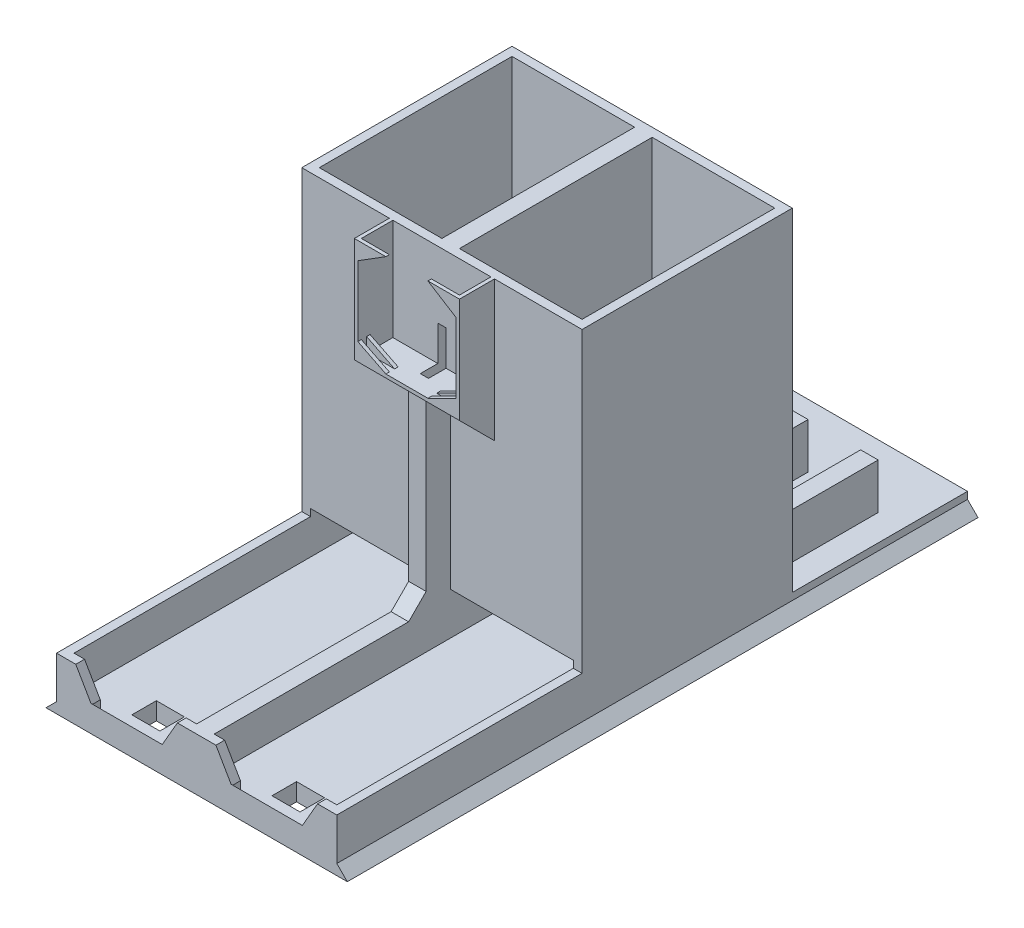
SolidWorks part; units mm, degrees
ref_plane "Front Plane" through (0, 0, 0) normal (0, 0, 1) x (1, 0, 0)
ref_plane "Top Plane" through (0, 0, 0) normal (0, 1, 0) x (1, 0, 0)
ref_plane "Right Plane" through (0, 0, 0) normal (1, 0, 0) x (0, 0, -1)
sketch "Sketch1" plane through (0, 0, 0) normal (0, 1, 0) x (1, 0, 0)
  line L1 (0, 0) -> (80, 0)
  line L2 (0, 0) -> (0, 60)
  line L3 (0, 60) -> (80, 60)
  line L4 (80, 0) -> (80, 60)
sketch "Sketch2" plane through (0, 0, 0) normal (0, 1, 0) x (1, 0, 0)
  line L1 (2.5, 57.5) -> (37.5, 57.5)
  line L2 (2.5, 57.5) -> (2.5, 2.5)
  line L3 (2.5, 2.5) -> (37.5, 2.5)
  line L4 (37.5, 57.5) -> (37.5, 2.5)
  line L5 (42.5, 57.5) -> (77.5, 57.5)
  line L6 (42.5, 57.5) -> (42.5, 2.5)
  line L7 (42.5, 2.5) -> (77.5, 2.5)
  line L8 (77.5, 57.5) -> (77.5, 2.5)
  dimension "D1" = 35
extrude "Boss-Extrude1" add sketch "Sketch1" along normal blind 100
extrude "Cut-Extrude1" cut sketch "Sketch2" along normal blind 95 from offset 5
sketch "Sketch3" plane through (0, 0, 0) normal (0, 0, 1) x (1, 0, 0)
  line L0 (80, 100) -> (80, 0) construction
  line L1 (0, 0) -> (80, 0)
  line L2 (0, 0) -> (0, 5)
  line L3 (0, 5) -> (80, 5)
  line L4 (80, 0) -> (80, 5)
extrude "Boss-Extrude2" add sketch "Sketch3" along normal blind 70
sketch "Sketch4" plane through (0, 5, 0) normal (0, 1, 0) x (1, 0, 0)
  line L0 (80, 0) -> (77.5, 0)
  line L5 (0, 0) -> (0, -70)
  line L18 (0, -70) -> (80, -70)
  line L19 (80, -70) -> (80, 0)
  line L20 (80, 0) -> (0, 0) construction
  line L21 (77.5, 0) -> (77.5, -67.5)
  line L22 (77.5, -67.5) -> (42.5, -67.5)
  line L23 (42.5, -67.5) -> (42.5, 0)
  line L24 (0, 0) -> (80, 0) construction
  line L25 (42.5, 0) -> (37.5, 0)
  line L26 (37.5, 0) -> (37.5, -67.5)
  line L27 (37.5, -67.5) -> (2.5, -67.5)
  line L28 (2.5, -67.5) -> (2.5, 0)
  line L29 (2.5, 0) -> (0, 0)
extrude "Boss-Extrude3" add sketch "Sketch4" along normal blind 10
sketch "Sketch5" plane through (0, 15, 0) normal (0, 1, 0) x (1, 0, 0)
  line L0 (37.5, -67.5) -> (2.5, -67.5) construction
  line L1 (10, -67.5) -> (30, -67.5)
  line L2 (10, -67.5) -> (10, -70)
  line L3 (10, -70) -> (30, -70)
  line L4 (30, -67.5) -> (30, -70)
  line L5 (0, -70) -> (80, -70) construction
  line L6 (77.5, -67.5) -> (42.5, -67.5) construction
  line L7 (70, -67.5) -> (50, -67.5)
  line L8 (70, -67.5) -> (70, -70)
  line L9 (70, -70) -> (50, -70)
  line L10 (50, -67.5) -> (50, -70)
  line L12 (37.5, 0) -> (37.5, -67.5) construction
  line L13 (42.5, -67.5) -> (42.5, 0) construction
  line L14 (77.5, 0) -> (77.5, -67.5) construction
  line L15 (2.5, -67.5) -> (2.5, 0) construction
  dimension "D1" = 7.5
  dimension "D2" = 7.5
  dimension "D3" = 7.5
  dimension "D4" = 7.5
extrude "Cut-Extrude2" cut sketch "Sketch5" against normal blind 7.5
sketch "Sketch6" plane through (0, 0, 0) normal (0, 0, 1) x (1, 0, 0)
  line L1 (2.5, 17) -> (37.5, 17)
  line L2 (2.5, 17) -> (2.5, 5)
  line L3 (2.5, 5) -> (37.5, 5)
  line L4 (37.5, 17) -> (37.5, 5)
  line L5 (42.5, 5) -> (77.5, 5)
  line L6 (42.5, 5) -> (42.5, 17)
  line L7 (42.5, 17) -> (77.5, 17)
  line L8 (77.5, 5) -> (77.5, 17)
extrude "Cut-Extrude4" cut sketch "Sketch6" against normal blind 57.5
sketch "Sketch7" plane through (0, 0, -60) normal (0, 0, -1) x (-1, 0, 0)
  circle A0 centre (-20, 11.5) radius 4
  circle A1 centre (-60, 11.5) radius 4
extrude "Cut-Extrude6" cut sketch "Sketch7" against normal up to next
sketch "Sketch9" plane through (0, 0, 0) normal (0, 1, 0) x (1, 0, 0)
  line L1 (0, 60) -> (80, 60)
  line L2 (0, 60) -> (0, 110)
  line L3 (0, 110) -> (80, 110)
  line L4 (80, 60) -> (80, 110)
extrude "Boss-Extrude4" add sketch "Sketch9" along normal blind 5
sketch "Sketch13" plane through (0, 5, 0) normal (0, 1, 0) x (1, 0, 0)
  line L1 (16, -64.5) -> (24, -64.5)
  line L2 (16, -64.5) -> (16, -57.5)
  line L3 (16, -57.5) -> (24, -57.5)
  line L4 (24, -64.5) -> (24, -57.5)
  line L5 (30, -67.5) -> (10, -67.5) construction
  line L10 (2.5, 57.5) -> (2.5, -67.5) construction
  line L11 (37.5, -67.5) -> (37.5, 57.5) construction
  line L12 (40, -70) -> (40, -52.9537) construction
  line L13 (30, -70) -> (50, -70) construction
  line L15 (56, -64.5) -> (56, -57.5)
  line L16 (64, -57.5) -> (56, -57.5)
  line L17 (64, -64.5) -> (64, -57.5)
  line L18 (64, -64.5) -> (56, -64.5)
  point P12 (16, -61)
  dimension "D1" = 13.5
  dimension "D2" = 13.5
  dimension "D3" = 7
  dimension "D4" = 3
extrude "Cut-Extrude8 (Button Holes)" cut sketch "Sketch13" against normal through all
sketch "Sketch14" plane through (0, 0, 0) normal (0, 0, 1) x (1, 0, 0)
  line L0 (0, 100) -> (80, 100) construction
  line L1 (25, 100) -> (26, 100)
  line L2 (25, 100) -> (25, 70)
  line L3 (25, 70) -> (26, 70)
  line L4 (26, 100) -> (26, 71)
  line L6 (54, 100) -> (55, 100)
  line L7 (54, 100) -> (54, 71)
  line L8 (54, 70) -> (55, 70)
  line L9 (55, 100) -> (55, 70)
  line L10 (26, 70) -> (54, 70)
  line L12 (26, 71) -> (54, 71)
  dimension "D1" = 30
  dimension "D2" = 1
  dimension "D3" = 1
extrude "Boss-Extrude5 (OLED Mount)" add sketch "Sketch14" along normal blind 10
sketch "Sketch15" plane through (0, 0, 10) normal (0, 0, 1) x (1, 0, 0)
  line L6 (40, 70) -> (40, 81.9127) construction
  line L7 (25, 70) -> (55, 70) construction
  line L8 (26, 71) -> (26, 100) construction
  line L14 (26, 71) -> (34, 71)
  line L15 (54, 71) -> (26, 71) construction
  line L16 (34, 71) -> (26, 75)
  line L17 (26, 75) -> (26, 71)
  line L18 (54, 75) -> (54, 71)
  line L19 (46, 71) -> (54, 75)
  line L20 (54, 71) -> (46, 71)
  dimension "D1" = 8
  dimension "D2" = 4
  dimension "D3" = 14
sketch "Sketch17" plane through (0, 0, 10) normal (0, 0, 1) x (1, 0, 0)
  line L0 (40, 100) -> (40, 89.7245) construction
  line L9 (26, 100) -> (54, 100) construction
  line L10 (54, 95) -> (54, 100)
  line L11 (46, 100) -> (54, 95)
  line L12 (26, 100) -> (34, 100)
  line L13 (34, 100) -> (26, 95)
  line L14 (26, 71) -> (26, 100) construction
  line L15 (26, 95) -> (26, 100)
  line L16 (54, 100) -> (46, 100)
  dimension "D1" = 8
  dimension "D2" = 5
extrude "Boss-Extrude6 (OLED Mount)" add sketch "Sketch15" against normal blind 1
extrude "Boss-Extrude7 (OLED Mount)" add sketch "Sketch15<2>" against normal blind 1 from offset 2.5 offset against normal yes
sketch "Sketch15<2>" plane through (0, 0, 10) normal (0, 0, 1) x (1, 0, 0) same geometry as "Sketch15"
extrude "Boss-Extrude8 (OLED Mount)" add sketch "Sketch17" against normal blind 1
sketch "Sketch32" plane through (25, 0, 0) normal (-1, 0, 0) x (0, 0, 1)
  line L0 (0, 70) -> (10, 70)
  line L1 (10, 70) -> (0, 60)
  line L3 (0, 60) -> (0, 70)
  line L4 (0, 15) -> (0, 17) construction
extrude "Boss-Extrude13 OLED Mount Support)" add sketch "Sketch32" against normal blind 30
sketch "Sketch18" plane through (0, 71, 0) normal (0, 1, 0) x (1, 0, 0)
  line L0 (26, 0) -> (54, 0) construction
  line L5 (42.5, 57.5) -> (42.5, -67.5) construction
  line L8 (38.82, 3) -> (41.18, 3)
  line L9 (38.82, 3) -> (38.82, -5)
  line L10 (38.82, -5) -> (41.18, -5)
  line L11 (41.18, 3) -> (41.18, -5)
  line L12 (37.5, -67.5) -> (37.5, 57.5) construction
  dimension "D1" = 1.32
  dimension "D2" = 1.32
  dimension "D3" = 3
  dimension "D4" = 5
extrude "Cut-Extrude9 (OLED Cable)" cut sketch "Sketch18" against normal through all and the other way blind 10
sketch "Sketch31" plane through (0, 15, 0) normal (0, 1, 0) x (1, 0, 0)
  line L0 (37.5, 0) -> (38.82, 0)
  line L1 (38.82, 0) -> (38.82, -5)
  line L2 (38.82, -5) -> (41.18, -5)
  line L3 (41.18, -5) -> (41.18, 0)
  line L4 (41.18, 0) -> (42.5, 0)
  line L5 (42.5, 0) -> (42.5, -7)
  line L6 (42.5, -7) -> (37.5, -7)
  line L7 (37.5, 0) -> (37.5, -67.5) construction
  line L8 (37.5, -7) -> (37.5, 0)
  dimension "D1" = 2
extrude "Boss-Extrude12 (OLED Cable Guide)" add sketch "Sketch31" along normal up to next
sketch "Sketch20" plane through (0, 5, 0) normal (0, 1, 0) x (1, 0, 0)
  line L0 (0, 60) -> (80, 60) construction
  line L1 (62.5, 60) -> (57.5, 60)
  line L2 (62.5, 60) -> (62.5, 65)
  line L3 (62.5, 65) -> (57.5, 65)
  line L4 (57.5, 60) -> (57.5, 65)
  line L5 (80, 60) -> (80, 110) construction
  line L7 (40, 110) -> (40, 60) construction
  line L8 (80, 110) -> (0, 110) construction
  line L9 (17.5, 65) -> (22.5, 65)
  line L10 (22.5, 60) -> (22.5, 65)
  line L11 (17.5, 60) -> (22.5, 60)
  line L12 (17.5, 60) -> (17.5, 65)
  point P8 (60, 60)
  dimension "D1" = 5
  dimension "D2" = 17.5
  dimension "D3" = 5
  dimension "D4" = 40
extrude "Cut-Extrude10 (Solenoid Wire Hole)" cut sketch "Sketch20" against normal through all
sketch "Sketch21" plane through (0, 5, 0) normal (0, 1, 0) x (1, 0, 0)
  line L0 (62.5, 60) -> (80, 60) construction
  line L1 (67.5, 60) -> (72.5, 60)
  line L2 (67.5, 60) -> (67.5, 92)
  line L3 (67.5, 92) -> (72.5, 92)
  line L4 (72.5, 60) -> (72.5, 92)
  line L7 (80, 110) -> (0, 110) construction
  line L9 (40, 60) -> (40, 110) construction
  line L10 (22.5, 60) -> (57.5, 60) construction
  line L11 (0, 110) -> (0, 60) construction
  line L12 (60, 110) -> (60, 60) construction
  line L13 (80, 60) -> (80, 110) construction
  line L15 (47.5, 60) -> (47.5, 92)
  line L16 (52.5, 92) -> (47.5, 92)
  line L17 (52.5, 60) -> (52.5, 92)
  line L18 (52.5, 60) -> (47.5, 60)
  line L19 (27.5, 60) -> (32.5, 60)
  line L20 (27.5, 60) -> (27.5, 92)
  line L21 (32.5, 60) -> (32.5, 92)
  line L22 (27.5, 92) -> (32.5, 92)
  line L23 (7.5, 60) -> (7.5, 92)
  line L24 (12.5, 92) -> (7.5, 92)
  line L25 (12.5, 60) -> (12.5, 92)
  line L26 (12.5, 60) -> (7.5, 60)
  dimension "D1" = 5
  dimension "D2" = 40
  dimension "D3" = 20
  dimension "D4" = 7.5
  dimension "D5" = 32
extrude "Boss-Extrude9 (Solenoid Side Support)" add sketch "Sketch21" along normal blind 13
chamfer "Chamfer3 (Thumb)" distance 2.5 angle 45 2 edges at (20, 7.5, 67.5) (60, 7.5, 67.5)
chamfer "Chamfer5 (Thumb)" distance 4.5 angle 60 4 edges at (70, 15, 68.75) (50, 15, 68.75) (30, 15, 68.75) (10, 15, 68.75) first distance on face at (75.8333, 15, 45.8333) first distance on face at (40, 15, 53) first distance on face at (4.1667, 15, 45.8333)
sketch "Sketch37" plane through (0, 0, 70) normal (0, 0, 1) x (1, 0, 0)
  line L0 (80, 0) -> (83, 0)
  line L1 (83, 0) -> (80, 3)
  line L2 (80, 0) -> (80, 15) construction
  line L3 (80, 3) -> (80, 0)
  line L4 (0, 0) -> (-3, 0)
  line L5 (-3, 0) -> (0, 3)
  line L6 (0, 15) -> (0, 0) construction
  line L7 (0, 3) -> (0, 0)
  dimension "D1" = 3
  dimension "D2" = 3
  dimension "D3" = 3
  dimension "D4" = 3
extrude "Boss-Extrude5 (Guide)" add sketch "Sketch37" against normal through all
sketch "Sketch49" plane through (0, 15, 0) normal (0, 1, 0) x (1, 0, 0)
  line L0 (42.5, -67.5) -> (42.5, -7) construction
  line L1 (37.5, -7) -> (42.5, -7)
  line L2 (37.5, -7) -> (37.5, -12)
  line L3 (37.5, -12) -> (42.5, -12)
  line L4 (42.5, -7) -> (42.5, -12)
  dimension "D1" = 5
extrude "Boss-Extrude14" add sketch "Sketch49" along normal blind 5
chamfer "Chamfer8" distance 5 angle 45 1 edges at (40, 20, 12)
